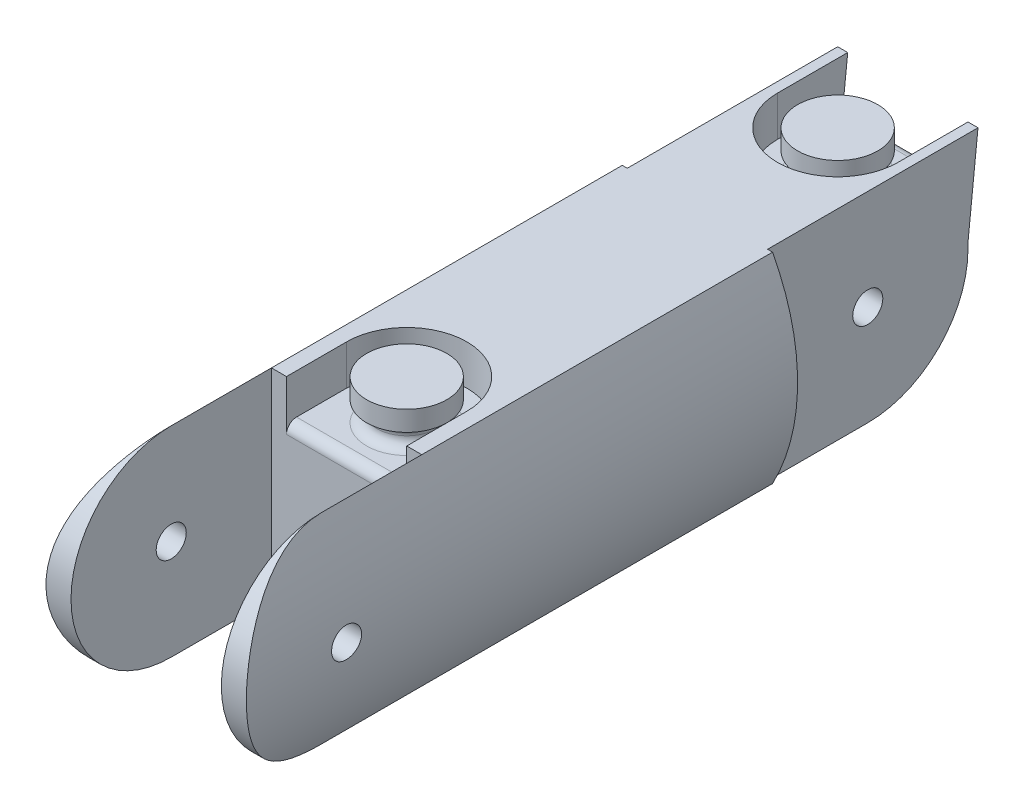
SolidWorks part; units mm, degrees
ref_plane "Alzado" through (0, 0, 0) normal (0, 0, 1) x (1, 0, 0)
ref_plane "Planta" through (0, 0, 0) normal (0, 1, 0) x (1, 0, 0)
ref_plane "Vista lateral" through (0, 0, 0) normal (1, 0, 0) x (0, 0, -1)
sketch "Croquis2" plane through (0, 0, 0) normal (0, 0, 1) x (1, 0, 0)
  line L5 (-7.5, -10) -> (7.5, -10)
  line L7 (-7.5, 10) -> (7.5, 10)
  line L9 (-7.5, -10) -> (7.5, 10) construction
  line L10 (-7.5, 10) -> (7.5, -10) construction
  arc A2 (-7.5, 10) -> (-7.5, -10) centre (11.25, 0) ccw
  arc A3 (7.5, -10) -> (7.5, 10) centre (-11.25, 0) ccw
  point P0 (0, 0)
  dimension "D1" = 15
  dimension "D2" = 20
extrude "Saliente-Extruir2" add sketch "Croquis2" along normal blind 55
sketch "Croquis4" plane through (0, 0, 0) normal (0, 0, -1) x (-1, 0, 0)
  line L1 (7.5, -10) -> (-7.5, -10) construction
  circle A0 centre (0, -7) radius 1.5
  dimension "D2" = 3
  dimension "D1" = 3
extrude "Cortar-Extruir1" cut sketch "Croquis4" against normal blind 50
sketch "Croquis3" plane through (0, 0, 0) normal (0, 0, -1) x (-1, 0, 0)
  line L8 (7.5, -10) -> (-7.5, -10) construction
  line L10 (7, 10) -> (7, -10)
  line L11 (7, -10) -> (3, -10)
  line L12 (-7, 10) -> (-7, -10)
  line L13 (7, 10) -> (-7, -10) construction
  line L14 (7, -10) -> (-7, 10) construction
  line L16 (3, -3) -> (3, -10)
  line L17 (-3, -10) -> (-7, -10)
  line L19 (-3, -3) -> (3, -3)
  line L20 (-3, -3) -> (-3, -10)
  line L21 (-7, 10) -> (7, 10)
  point P0 (0, 0)
  dimension "D1" = 14
  dimension "D2" = 4
  dimension "D3" = 4
  dimension "D4" = 7
extrude "Saliente-Extruir3" add sketch "Croquis3" along normal blind 20
sketch "Croquis8" plane through (-7, 0, 0) normal (-1, 0, 0) x (0, 0, 1)
  line L0 (-20, -10) -> (-20, 10) construction
  line L1 (-20, -10) -> (0, -10) construction
  circle A0 centre (-10, 0) radius 1.5
  point P4 (-20, 0)
  dimension "D1" = 3
  dimension "D2" = 10
  dimension "D3" = 10
extrude "Cortar-Extruir4" cut sketch "Croquis8" against normal blind 14
fillet "Redondeo1" radius 10 2 edges at (-5, -10, -20) (5, -10, -20)
sketch "Croquis6" plane through (0, 0, 55) normal (0, 0, 1) x (1, 0, 0)
  line L1 (-7.5, 10) -> (7.5, 10)
  line L2 (-7.5, 10) -> (-7.5, -10)
  line L3 (-7.5, -10) -> (7.5, -10)
  line L4 (7.5, 10) -> (7.5, -10)
extrude "Cortar-Extruir2" cut sketch "Croquis6" against normal blind 20
sketch "Croquis7" plane through (0, 0, 0) normal (1, 0, 0) x (0, 0, -1)
  line L0 (-55, 10) -> (-55, -10) construction
  line L2 (-45, -10) -> (-60, -10)
  line L4 (-45, 10) -> (-60, 10)
  line L5 (-60, -10) -> (-60, 10)
  arc A0 (-45, 10) -> (-45, -10) centre (-45, 0) ccw
  circle A1 centre (-45, 0) radius 1.5
  dimension "D3" = 10
  dimension "D4" = 3
  dimension "D1" = 10
  dimension "D2" = 15
  dimension "D5" = 20
extrude "Cortar-Extruir3" cut sketch "Croquis7" against normal through all both and the other way through all
sketch "Sketch1" plane through (0, 10, 0) normal (0, 1, 0) x (1, 0, 0)
  line L0 (7.5, -35) -> (-7.5, -35) construction
  line L1 (-7, 20) -> (7, 20) construction
  line L4 (-6, 14) -> (-6, 20)
  line L5 (-6, 20) -> (6, 20)
  line L6 (6, 14) -> (6, 20)
  line L8 (-6, -29) -> (-6, -35)
  line L9 (-6, -35) -> (6, -35)
  line L10 (6, -29) -> (6, -35)
  arc A0 (-6, 14) -> (6, 14) centre (0, 14) ccw
  arc A1 (6, -29) -> (-6, -29) centre (0, -29) ccw
  dimension "D1" = 12
  dimension "D2" = 12
  dimension "D3" = 6
  dimension "D4" = 6
extrude "Cut-Extrude1" cut sketch "Sketch1" against normal blind 4
sketch "Sketch2" plane through (0, 6, 0) normal (0, 1, 0) x (1, 0, 0)
  circle A0 centre (0, -29) radius 3
  circle A1 centre (0, 14) radius 3
  dimension "D1" = 6
  dimension "D2" = 6
extrude "Boss-Extrude1" add sketch "Sketch2" along normal blind 2
sketch "Sketch3" plane through (0, 8, 0) normal (0, 1, 0) x (1, 0, 0)
  circle A0 centre (0, 14) radius 4
  circle A1 centre (0, -29) radius 4
  dimension "D1" = 8
  dimension "D2" = 8
extrude "Boss-Extrude2" add sketch "Sketch3" along normal blind 2
fillet "Fillet1" radius 1 4 edges at (0, 8, -11) (0, 6, -11) (0, 8, 32) (0, 6, 32)
fillet "Fillet2" radius 1 2 edges at (0, 6, 35) (0, 6, -20)
fillet "Fillet3" radius 1 2 edges at (-1.5, -7, 0) (1.5, -7, 35)
sketch "Sketch4" plane through (7, 0, 0) normal (1, 0, 0) x (0, 0, -1)
  line L0 (20, 10) -> (21, 10)
  line L1 (21, 10) -> (19.666, -2.5629)
  line L2 (19.666, -2.5629) -> (20, 10)
  arc A0 (10, -10) -> (20, 0) centre (10, 0) ccw construction
  dimension "D1" = 1
sketch "Sketch5" plane through (-7, 0, 0) normal (-1, 0, 0) x (0, 0, 1)
  line L0 (-20, 10) -> (-21, 10)
  line L1 (-21, 10) -> (-19.666, -2.5629)
  line L2 (-19.666, -2.5629) -> (-20, 10)
extrude "Boss-Extrude3" add sketch "Sketch4" against normal blind 1
extrude "Boss-Extrude4" add sketch "Sketch5" against normal blind 1
